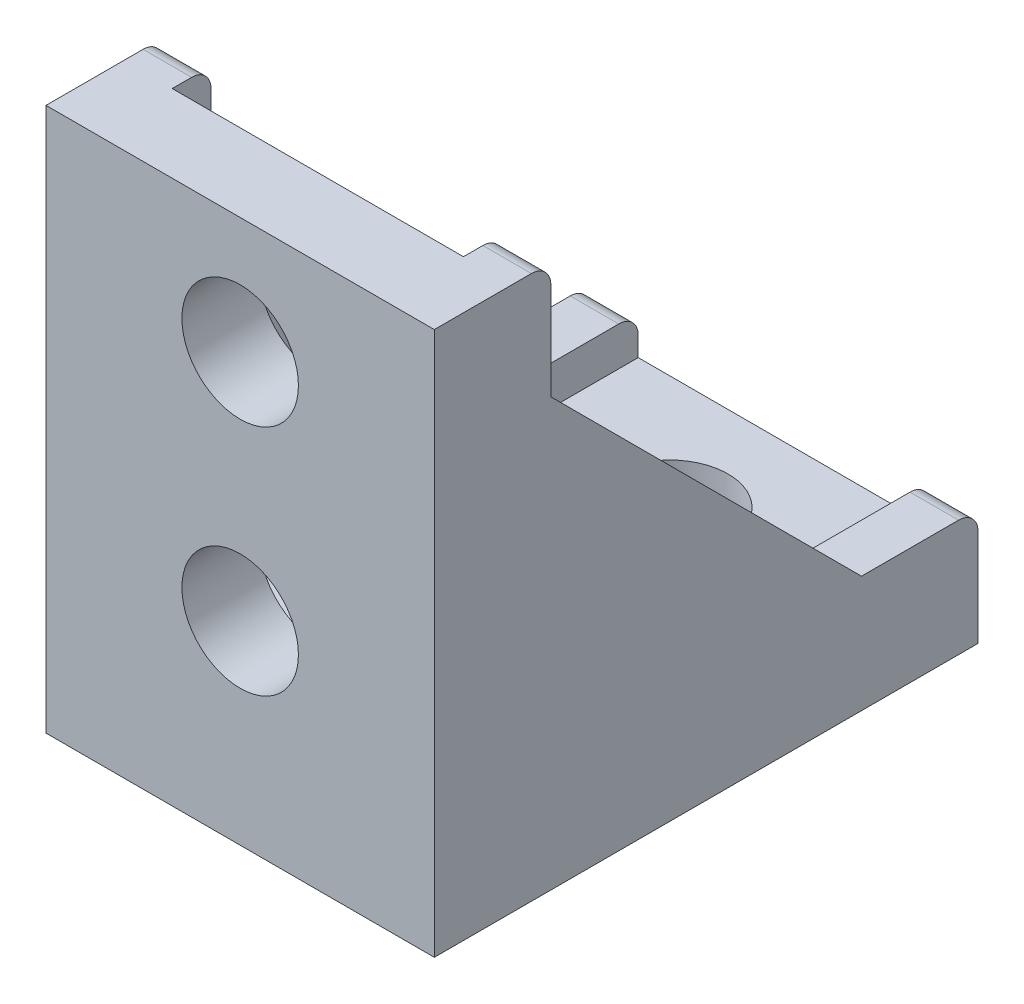
SolidWorks part; units mm, degrees
ref_plane "Front Plane" through (0, 0, 0) normal (0, 0, 1) x (1, 0, 0)
ref_plane "Top Plane" through (0, 0, 0) normal (0, 1, 0) x (1, 0, 0)
ref_plane "Right Plane" through (0, 0, 0) normal (1, 0, 0) x (0, 0, -1)
sketch "Sketch1" plane through (0, 0, 0) normal (0, 0, 1) x (1, 0, 0)
  line L0 (-10, 6) -> (7.5, 6)
  line L1 (7.5, 6) -> (7.5, 22)
  line L2 (7.5, 22) -> (-10, 22)
  line L3 (-10, 22) -> (-10, 6)
extrude "Boss-Extrude1" add sketch "Sketch1" against normal blind 6
sketch "Sketch2" plane through (0, 0, -6) normal (0, 0, -1) x (-1, 0, 0)
  line L0 (10, 22) -> (10, 6)
  line L1 (10, 6) -> (7.5, 6)
  line L2 (7.5, 6) -> (7.5, 22)
  line L3 (7.5, 22) -> (10, 22)
extrude "Boss-Extrude2" add sketch "Sketch2" along normal blind 22
sketch "Sketch3" plane through (7.5, 0, 0) normal (1, 0, 0) x (0, 0, -1)
  line L0 (6, 22) -> (22, 6)
  line L1 (22, 6) -> (0, 6)
  line L2 (0, 6) -> (0, 22)
  line L3 (0, 22) -> (6, 22)
extrude "Boss-Extrude3" add sketch "Sketch3" along normal blind 2.5
sketch "Sketch4" plane through (0, 22, 0) normal (0, 1, 0) x (-1, 0, 0)
  line L0 (7.5, -6) -> (-10, -6)
  line L1 (-10, -6) -> (-10, 0)
  line L2 (-10, 0) -> (10, 0)
  line L3 (10, 0) -> (10, -28)
  line L4 (10, -28) -> (7.5, -28)
  line L5 (7.5, -28) -> (7.5, -6)
extrude "Boss-Extrude4" add sketch "Sketch4" along normal blind 6
sketch "Sketch5" plane through (0, 6, 0) normal (0, -1, 0) x (1, 0, 0)
  line L0 (-10, 0) -> (10, 0)
  line L1 (10, 0) -> (10, -28)
  line L2 (10, -28) -> (-10, -28)
  line L3 (-10, -28) -> (-10, 0)
extrude "Boss-Extrude5" add sketch "Sketch5" along normal blind 6
ref_plane "Plane1" through (0, 0, -6) normal (0, 0, -1) x (-1, 0, 0)
ref_plane "Plane2" through (0, 0, -4) normal (0, 0, 1) x (1, 0, 0)
sketch "Sketch7" plane through (0, 0, -4) normal (0, 0, 1) x (1, 0, 0)
  line L0 (-7.5, 6) -> (7.5, 6)
  line L1 (7.5, 6) -> (7.5, 28)
  line L2 (7.5, 28) -> (-7.5, 28)
  line L3 (-7.5, 28) -> (-7.5, 6)
extrude "Cut-Extrude1" cut sketch "Sketch7" against normal up to surface up to plane "Plane1"
ref_plane "Plane3" through (0, 6, 0) normal (0, 1, 0) x (1, 0, 0)
ref_plane "Plane4" through (0, 4, 0) normal (0, -1, 0) x (1, 0, 0)
sketch "Sketch9" plane through (0, 4, 0) normal (0, -1, 0) x (1, 0, 0)
  line L0 (-7.5, -4) -> (-7.5, -28)
  line L1 (-7.5, -28) -> (7.5, -28)
  line L2 (7.5, -28) -> (7.5, -4)
  line L3 (7.5, -4) -> (-7.5, -4)
extrude "Cut-Extrude2" cut sketch "Sketch9" against normal up to surface up to plane "Plane3"
sketch "Sketch10" plane through (-10, 0, 0) normal (-1, 0, 0) x (0, 0, 1)
  line L0 (-28, 28) -> (-28, 6)
  line L1 (-28, 6) -> (-22, 6)
  line L2 (-22, 6) -> (-6, 22)
  line L3 (-6, 22) -> (-6, 28)
  line L4 (-6, 28) -> (-28, 28)
extrude "Cut-Extrude3" cut sketch "Sketch10" against normal through all
sketch "Sketch11" plane through (0, 0, -4) normal (0, 0, -1) x (-1, 0, 0)
  line L0 (3.25, 12.5) -> (3.25, 18)
  line L1 (-3.25, 18) -> (-3.25, 12.5)
  arc A0 (3.25, 18) -> (-3.25, 18) centre (0, 18) ccw
  arc A1 (-3.25, 12.5) -> (3.25, 12.5) centre (0, 12.5) ccw
extrude "Cut-Extrude4" cut sketch "Sketch11" against normal through all
sketch "Sketch12" plane through (0, 0, 0) normal (0, -1, 0) x (1, 0, 0)
  line L0 (3.25, -18) -> (3.25, -12.5)
  line L1 (-3.25, -12.5) -> (-3.25, -18)
  arc A0 (-3.25, -18) -> (3.25, -18) centre (0, -18) ccw
  arc A1 (3.25, -12.5) -> (-3.25, -12.5) centre (0, -12.5) ccw
extrude "Cut-Extrude5" cut sketch "Sketch12" against normal through all
ref_plane "Plane5" through (3, 0, 0) normal (1, 0, 0) x (0, 0, -1)
sketch "Sketch13" plane through (3, 0, 0) normal (1, 0, 0) x (0, 0, -1)
  line L0 (0, 26.5) -> (-1.6, 24.9)
  line L1 (-1.6, 24.9) -> (-1.6, 23.5)
  line L2 (-1.6, 23.5) -> (0, 23.5)
  line L3 (0, 23.5) -> (0, 26.5)
extrude "Boss-Extrude6" add sketch "Sketch13" against normal blind 6
sketch "Sketch14" plane through (3, 0, 0) normal (1, 0, 0) x (0, 0, -1)
  line L0 (0, 6.5) -> (-1.6, 4.9)
  line L1 (-1.6, 4.9) -> (-1.6, 3.5)
  line L2 (-1.6, 3.5) -> (0, 3.5)
  line L3 (0, 3.5) -> (0, 6.5)
extrude "Boss-Extrude7" add sketch "Sketch14" against normal blind 6
sketch "Sketch15" plane through (3, 0, 0) normal (1, 0, 0) x (0, 0, -1)
  line L0 (23.5, 0) -> (23.5, -1.6)
  line L1 (23.5, -1.6) -> (24.9, -1.6)
  line L2 (24.9, -1.6) -> (26.5, 0)
  line L3 (26.5, 0) -> (23.5, 0)
extrude "Boss-Extrude8" add sketch "Sketch15" against normal blind 6
sketch "Sketch16" plane through (3, 0, 0) normal (1, 0, 0) x (0, 0, -1)
  line L0 (3.5, 0) -> (3.5, -1.6)
  line L1 (3.5, -1.6) -> (4.9, -1.6)
  line L2 (4.9, -1.6) -> (6.5, 0)
  line L3 (6.5, 0) -> (3.5, 0)
extrude "Boss-Extrude9" add sketch "Sketch16" against normal blind 6
fillet "Fillet1" radius 1 4 edges at (-8.75, 6, -28) (8.75, 6, -28) (-8.75, 28, -6) (8.75, 28, -6) tangent propagation no
sketch "Sketch17" plane through (0, 4, 0) normal (0, 1, 0) x (1, 0, 0)
  line L1 (-7.5, 28) -> (7.5, 28)
  line L2 (-7.5, 28) -> (-7.5, 4)
  line L3 (-7.5, 4) -> (7.5, 4)
  line L4 (7.5, 28) -> (7.5, 4)
extrude "Boss-Extrude10" add sketch "Sketch17" against normal up to surface (4 mm away) up to face at (0, 0, -25)
sketch "Sketch18" plane through (0, 0, -4) normal (0, 0, -1) x (-1, 0, 0)
  line L1 (-7.5, 28) -> (7.5, 28)
  line L2 (-7.5, 28) -> (-7.5, 4)
  line L3 (-7.5, 4) -> (7.5, 4)
  line L4 (7.5, 28) -> (7.5, 4)
extrude "Boss-Extrude11" add sketch "Sketch18" against normal up to surface (4 mm away) up to face at (0, 5, 0)
sketch "Sketch19" plane through (0, 4, 0) normal (0, 1, 0) x (1, 0, 0)
  line L0 (0, 4) -> (0, 28)
  line L1 (7.5, 4) -> (-7.5, 4) construction
  line L2 (-7.5, 28) -> (7.5, 28) construction
  line L3 (0, 28) -> (0, 16)
  line L4 (0, 16) -> (0, 28)
  line L5 (0, 22) -> (0, 22.1235)
  line L6 (0, 22.1235) -> (0, 16)
  line L7 (0, 4) -> (0, 10)
  circle A0 centre (0, 22.1235) radius 3
  circle A1 centre (0, 10) radius 3
  dimension "D3" = 6
  dimension "D4" = 6
  dimension "D1" = 6
  dimension "D2" = 6
sketch "Sketch20" plane through (0, 0, -4) normal (0, 0, -1) x (-1, 0, 0)
  line L0 (0, 28) -> (0, 4)
  line L1 (-7.5, 28) -> (7.5, 28) construction
  line L2 (3, 4) -> (-3, 4) construction
  line L3 (0, 4) -> (0, 16)
  line L4 (0, 16) -> (0, 22)
  line L5 (0, 16) -> (0, 10)
  circle A0 centre (0, 22) radius 3
  circle A1 centre (0, 10) radius 3
  dimension "D3" = 6
  dimension "D4" = 6
  dimension "D1" = 6
  dimension "D2" = 6
extrude "Cut-Extrude6" cut sketch "Sketch20" against normal blind 10 contours L0 A0 | L0 A0 | L3 A1 L5 | L5 A1 L3 region at (-1.2732, 22, -4) region at (-1.2732, 10, -4) region at (1.2732, 10, -4) region at (1.2732, 22, -4)
extrude "Cut-Extrude7" cut sketch "Sketch19" against normal blind 10 contours L6 A0 L0 L4 | L0 A0 L6 L4 | L7 A1 L0 | L0 A1 L7 region at (-1.2732, 4, -22.1235) region at (1.2732, 4, -22.1235) region at (1.2732, 4, -10) region at (-1.2732, 4, -10)
sketch "Sketch21" plane through (0, 3.5, 0) normal (0, -1, 0) x (1, 0, 0)
  line L1 (-3, 0) -> (3, 0)
  line L2 (-3, 0) -> (-3, 1.6)
  line L3 (-3, 1.6) -> (3, 1.6)
  line L4 (3, 0) -> (3, 1.6)
extrude "Cut-Extrude8" cut sketch "Sketch21" against normal through all both and the other way through all
sketch "Sketch22" plane through (0, 0, -3.5) normal (0, 0, 1) x (1, 0, 0)
  line L1 (-3, 0) -> (3, 0)
  line L2 (-3, 0) -> (-3, -1.6)
  line L3 (-3, -1.6) -> (3, -1.6)
  line L4 (3, 0) -> (3, -1.6)
extrude "Cut-Extrude9" cut sketch "Sketch22" against normal through all both contours L2 L1 L4 L3
